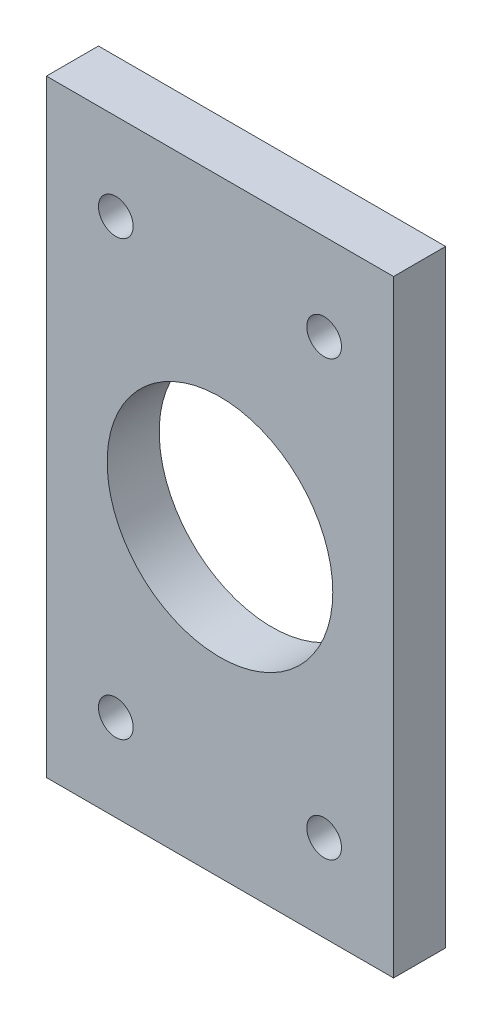
SolidWorks part; units mm, degrees
ref_plane "Front" through (0, 0, 0) normal (0, 0, 1) x (1, 0, 0)
ref_plane "Top" through (0, 0, 0) normal (0, 1, 0) x (1, 0, 0)
ref_plane "Right" through (0, 0, 0) normal (1, 0, 0) x (0, 0, -1)
sketch "草图1" plane through (0, 0, 0) normal (0, 0, 1) x (1, 0, 0)
  line L0 (-40, 0) -> (-40, 77) construction
  line L1 (-40, 0) -> (-40, 70)
  line L2 (0, 0) -> (0, 77) construction
  line L3 (0, 0) -> (0, 70)
  line L4 (-40, 70) -> (0, 70)
  line L6 (-40, 0) -> (0, 0)
  circle A0 centre (-20, 35) radius 13 construction
  circle A1 centre (-20, 35) radius 13
  point P8 (-40, 35)
  dimension "D1" = 70
extrude "凸台-拉伸1" add sketch "草图1" along normal blind 6 contours A1 | L1 L4 L3 L6
sketch "草图2" plane through (0, 0, 6) normal (0, 0, 1) x (1, 0, 0)
  line L0 (-32, 60) -> (-8, 60) construction
  line L1 (-40, 70) -> (0, 70) construction
  circle A0 centre (-32, 60) radius 2
  circle A1 centre (-8, 60) radius 2
  point P4 (-20, 60)
  dimension "D1" = 4
  dimension "D2" = 24
  dimension "D3" = 10
extrude "切除-拉伸1" cut sketch "草图2" against normal blind 10
ref_plane "基准面1" through (0, 35, 0) normal (0, 1, 0) x (1, 0, 0)
mirror "镜向1" about plane through (0, 35, 0) normal (0, 1, 0) of "切除-拉伸1"
